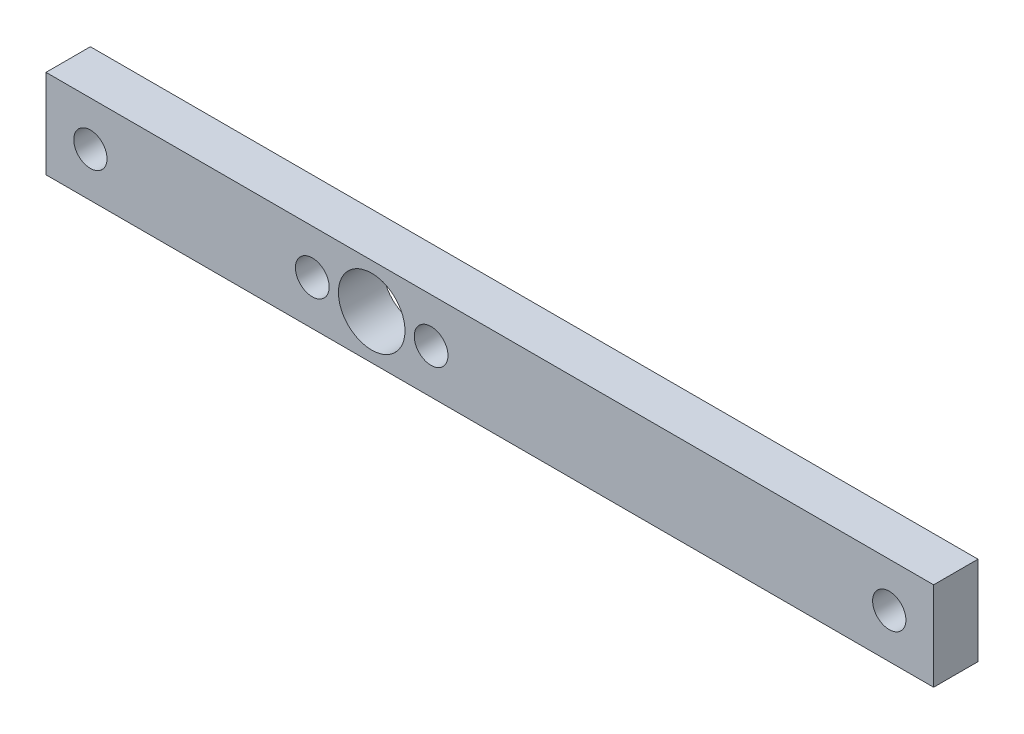
SolidWorks part; units mm, degrees
ref_plane "Front Plane" through (0, 0, 0) normal (0, 0, 1) x (1, 0, 0)
ref_plane "Top Plane" through (0, 0, 0) normal (0, 1, 0) x (1, 0, 0)
ref_plane "Right Plane" through (0, 0, 0) normal (1, 0, 0) x (0, 0, -1)
sketch "Sketch1" plane through (0, 0, 0) normal (0, 0, 1) x (1, 0, 0)
  line L1 (0, 0) -> (127, 0)
  line L2 (0, 0) -> (0, 12.7)
  line L3 (0, 12.7) -> (127, 12.7)
  line L4 (127, 0) -> (127, 12.7)
  circle A0 centre (38.1, 6.35) radius 2.413
  circle A1 centre (55.1, 6.35) radius 2.413
  circle A2 centre (6.35, 6.35) radius 2.3813
  circle A3 centre (120.65, 6.35) radius 2.3813
  circle A4 centre (46.6, 6.35) radius 4.7625
  dimension "D3" = 4.826
  dimension "D4" = 4.826
  dimension "D5" = 6.35
  dimension "D6" = 6.35
  dimension "D7" = 8.5
  dimension "D8" = 38.1
  dimension "D9" = 4.7625
  dimension "D10" = 6.35
  dimension "D11" = 6.35
  dimension "D12" = 4.7625
  dimension "D13" = 6.35
  dimension "D14" = 6.35
  dimension "D15" = 9.525
  dimension "D16" = 6.35
  dimension "D17" = 8.5
  dimension "D1" = 12.7
  dimension "D2" = 127
other "AlignGroup1"
extrude "Boss-Extrude1" add sketch "Sketch1" along normal blind 6.35
